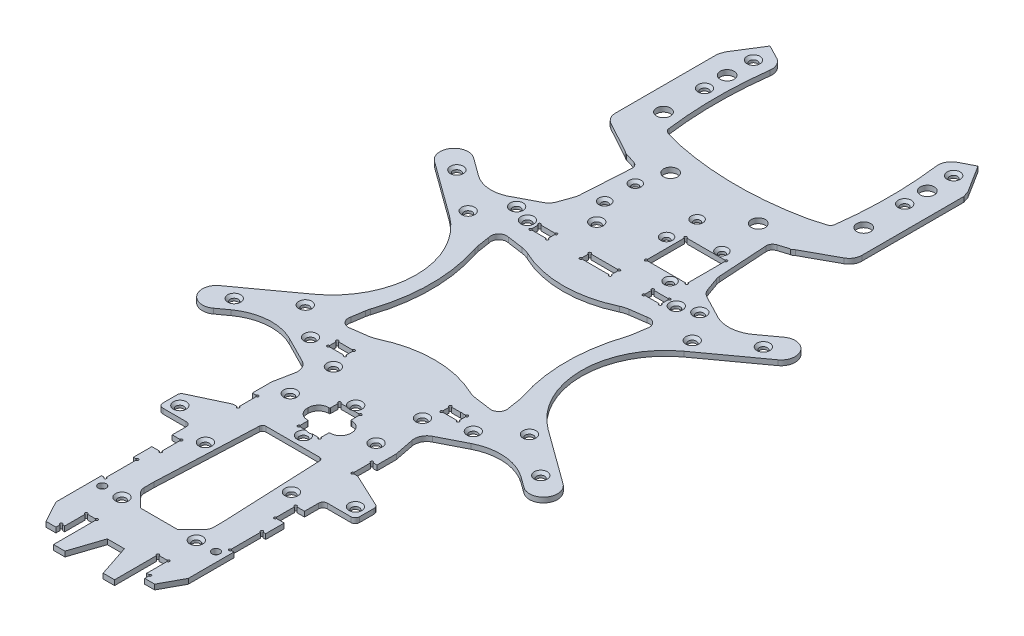
SolidWorks part; units mm, degrees
other "细节项目1"
other "细节项目5"
material "Thornel VCB-20 碳布"
ref_plane "前视基准面" through (0, 0, 0) normal (0, 0, 1) x (1, 0, 0)
ref_plane "上视基准面" through (0, 0, 0) normal (0, 1, 0) x (1, 0, 0)
ref_plane "右视基准面" through (0, 0, 0) normal (1, 0, 0) x (0, 0, -1)
sketch "草图1" plane through (0, 0, 0) normal (0, 1, 0) x (1, 0, 0)
  line L0 (-126.4995, 0) -> (116.8967, 0) construction
  line L1 (121.619, 121.619) -> (-121.619, -121.619) construction
  line L2 (0, 104.5414) -> (0, -99.6328) construction
  line L3 (-108.3893, 108.3893) -> (124.9236, -124.9236) construction
  line L4 (0, 0) -> (86.3378, -62.728) construction
  line L5 (15.4, 65.75) -> (23.6, 65.75)
  line L6 (15.4, 50.25) -> (15.4, 65.75)
  line L19 (15.4, 50.25) -> (23.6, 50.25)
  line L20 (30.4719, 81.4909) -> (48.4165, 91.3178)
  line L21 (0, 82.79) -> (0, 88.225) construction
  line L23 (-25.278, 96.1016) -> (-31.2014, 97.7723)
  line L25 (24.5, -95.1) -> (26.0011, -95.1) construction
  line L35 (67.5025, -42.245) -> (46.103, -26.6974)
  line L38 (-16.7464, -105.1066) -> (-17.9066, -103.9464) construction
  line L39 (-48.4165, 91.3178) -> (-48.4165, 134.3222)
  line L40 (-30.4719, 81.4909) -> (-48.4165, 91.3178)
  line L42 (26.0011, -95.1) -> (26.0011, -102.35)
  line L59 (-47.6512, 136.6895) -> (-40.8695, 147.4648)
  line L64 (15.4, 58) -> (27.0301, 58) construction
  line L65 (19.5, 65.75) -> (19.5, 50.25) construction
  line L66 (23.6, 65.75) -> (23.6, 50.25)
  line L69 (-39.335, 68.135) -> (3.7462, 68.135) construction
  line L72 (26.0011, -102.35) -> (22.5, -102.35)
  line L80 (-18.6137, -103.9464) -> (-19.7036, -105.0363) construction
  line L82 (4.1009, -74) -> (4.1009, -71.0475)
  line L83 (-3.6009, -74.5) -> (3.6009, -74.5)
  line L84 (3.6009, -58.5) -> (-3.5991, -58.5)
  line L85 (4.1009, -59) -> (4.1009, -61.9525)
  line L86 (-4.1009, -74) -> (-4.1009, -71.0461)
  line L87 (-4.1009, -61.9511) -> (-4.1009, -58.9981)
  line L88 (-4.5484, -70.6961) -> (-4.4509, -70.6961)
  line L89 (-8.5484, -66.6961) -> (-8.5484, -66.3011)
  line L90 (8.5484, -66.6975) -> (8.5484, -66.3025)
  line L91 (4.4509, -70.6975) -> (4.5484, -70.6975)
  line L92 (4.5484, -62.3025) -> (4.4509, -62.3025)
  line L93 (-4.5484, -62.3011) -> (-4.4509, -62.3011)
  line L97 (19, -62.5) -> (19, -100.5) construction
  line L98 (19, -100.5) -> (-19, -100.5) construction
  line L99 (-19, -62.5) -> (-19, -100.5) construction
  line L100 (22.5, -102.35) -> (22.5, -110.35)
  line L101 (16.1, -146) -> (16.1, -154.5)
  line L102 (16.1, -146) -> (12, -146)
  line L103 (12, -146) -> (12, -163)
  line L104 (17.45, -154.5) -> (16.1, -154.5)
  line L105 (17.45, -156.6) -> (17.45, -154.5)
  line L106 (-3.3584, -150.5) -> (-7.5, -163)
  line L107 (-7.5, -163) -> (-12, -163)
  line L108 (21.3534, -156.6) -> (17.45, -156.6)
  line L109 (-17.45, -156.6) -> (-17.45, -154.5)
  line L110 (-17.45, -154.5) -> (-16.1, -154.5)
  line L111 (-12, -146) -> (-12, -163)
  line L112 (-16.1, -146) -> (-12, -146)
  line L113 (-16.1, -146) -> (-16.1, -154.5)
  line L114 (7.5, -163) -> (12, -163)
  line L115 (-3.3584, -150.5) -> (3.3584, -150.5)
  line L116 (3.3584, -150.5) -> (7.5, -163)
  line L117 (-21.3534, -156.6) -> (-17.45, -156.6)
  line L118 (-13.5761, -121.8546) -> (-11.8487, -82.2911)
  line L119 (-12.5918, -128.1539) -> (-7.25, -133.5)
  line L120 (-7.25, -133.5) -> (7.25, -133.5)
  line L121 (-13.5793, -125.7684) -> (-13.5793, -122.0018)
  line L122 (22.5, -110.35) -> (26.0011, -110.35)
  line L123 (26.0011, -130.1) -> (26.0011, -148.0463)
  line L124 (26.0011, -148.0463) -> (21.3534, -156.6)
  line L125 (-26.0011, -148.0463) -> (-21.3534, -156.6)
  line L126 (-26.0011, -130.1) -> (-26.0011, -148.0463)
  line L127 (26.0011, -110.35) -> (26.0011, -117.6)
  line L128 (26.0011, -117.6) -> (24.5011, -117.6)
  line L129 (24.5011, -117.6) -> (24.5011, -130.1)
  line L130 (24.5011, -130.1) -> (26.0011, -130.1)
  line L132 (-24.5011, -130.1) -> (-26.0011, -130.1)
  line L133 (-24.5011, -117.6) -> (-24.5011, -130.1)
  line L134 (-26.0011, -117.6) -> (-24.5011, -117.6)
  line L135 (-26.0011, -110.35) -> (-26.0011, -117.6)
  line L136 (-22.5, -110.35) -> (-26.0011, -110.35)
  line L137 (-22.5, -102.35) -> (-22.5, -110.35)
  line L138 (-26.0011, -102.35) -> (-22.5, -102.35)
  line L139 (-26.0011, -95.1) -> (-26.0011, -102.35)
  line L140 (-24.5, -95.1) -> (-26.0011, -95.1) construction
  line L142 (-67.5025, 42.245) -> (-46.103, 26.6974)
  line L143 (-67.5025, -42.245) -> (-46.103, -26.6974)
  line L149 (48.4165, 91.3178) -> (48.4165, 134.3222)
  line L150 (0, -114.8485) -> (0, -146.3095) construction
  line L151 (-10.5, -81) -> (10.5, -81)
  line L152 (12.5918, -128.1539) -> (7.25, -133.5)
  line L153 (13.5793, -125.7684) -> (13.5793, -122.0018)
  line L154 (13.5761, -121.8546) -> (11.8487, -82.2911)
  line L155 (-19, -62.5) -> (19, -62.5) construction
  line L180 (67.5025, 42.245) -> (46.103, 26.6974)
  line L181 (44.0442, 32) -> (60.2246, 43.7557) construction
  line L183 (25.278, 96.1016) -> (31.2014, 97.7723)
  line L195 (61.0368, 51.1442) -> (53.9618, 46.0039)
  line L196 (30.4719, 81.4909) -> (34.3794, 54.2815)
  line L197 (-30.4719, 81.4909) -> (-34.3794, 54.2815)
  line L198 (-61.0368, 51.1442) -> (-53.9618, 46.0039)
  line L199 (57.02, -48.2258) -> (61.0368, -51.1442)
  line L200 (24.5, -64.7956) -> (24.5, -95.1) construction
  line L201 (-24.5, -64.7956) -> (-24.5, -95.1) construction
  line L202 (-57.02, -48.2258) -> (-61.0368, -51.1442)
  line L203 (26.0011, -95.1) -> (38.6804, -95.1)
  line L204 (38.6804, -95.1) -> (38.6804, -86.6)
  line L205 (38.6804, -86.6) -> (24.5, -79.9478)
  line L207 (-38.6804, -86.6) -> (-24.5, -79.9478)
  line L208 (-38.6804, -95.1) -> (-38.6804, -86.6)
  line L209 (-26.0011, -95.1) -> (-38.6804, -95.1)
  line L210 (-24.5, -64.7956) -> (-24.5, -79.9478) construction
  line L211 (-19.7036, -114.2434) -> (-18.5434, -115.4036) construction
  line L212 (-17.8363, -115.4036) -> (-16.7464, -114.3137) construction
  line L213 (-19.85, -105.3898) -> (-19.85, -113.8898) construction
  line L214 (-16.6, -105.4602) -> (-16.6, -113.9602) construction
  line L221 (-16.6, -105.4602) -> (-16.6, -108.5148) construction
  line L222 (-16.6, -108.5148) -> (-17.1, -109.0148) construction
  line L223 (-17.1, -109.0148) -> (-17.1, -110.2648) construction
  line L224 (-17.1, -110.2648) -> (-16.6, -110.7648) construction
  line L225 (-16.6, -110.7648) -> (-16.6, -113.9602) construction
  line L226 (-19.85, -109.6398) -> (-13.2317, -109.6398) construction
  line L227 (17.1, -110.2648) -> (16.6, -110.7648) construction
  line L228 (17.1, -109.0148) -> (17.1, -110.2648) construction
  line L229 (16.6, -108.5148) -> (17.1, -109.0148) construction
  line L230 (16.6, -105.4602) -> (16.6, -108.5148) construction
  line L231 (16.7464, -105.1066) -> (17.9066, -103.9464) construction
  line L232 (18.6137, -103.9464) -> (19.7036, -105.0363) construction
  line L233 (19.85, -105.3898) -> (19.85, -113.8898) construction
  line L234 (19.7036, -114.2434) -> (18.5434, -115.4036) construction
  line L235 (17.8363, -115.4036) -> (16.7464, -114.3137) construction
  line L236 (16.6, -110.7648) -> (16.6, -113.9602) construction
  line L237 (-24.5, -72.3717) -> (-22.5, -72.3717)
  line L238 (-22.5, -72.3717) -> (-22.5, -79.9478)
  line L239 (-22.5, -79.9478) -> (-24.5, -79.9478)
  line L240 (-24.5, -64.7956) -> (-24.5, -72.3717)
  line L241 (22.5, -79.9478) -> (24.5, -79.9478)
  line L242 (24.5, -64.7956) -> (24.5, -72.3717)
  line L243 (24.5, -72.3717) -> (22.5, -72.3717)
  line L244 (22.5, -72.3717) -> (22.5, -79.9478)
  line L245 (-40.8695, 147.4648) -> (-35.5107, 144.7028)
  line L246 (-47.6512, 136.6895) -> (-48.4165, 134.3222)
  line L247 (40.8695, 147.4648) -> (35.5107, 144.7028)
  line L248 (47.6512, 136.6895) -> (40.8695, 147.4648)
  line L249 (47.6512, 136.6895) -> (48.4165, 134.3222)
  circle A0 centre (10, 10) radius 1.075
  circle A1 centre (12.75, 12.75) radius 1.075
  circle A2 centre (15.25, 15.25) radius 1.55
  circle A3 centre (-15.25, 15.25) radius 1.55
  circle A4 centre (-12.75, 12.75) radius 1.075
  circle A5 centre (-10, 10) radius 1.075
  circle A6 centre (-10, -10) radius 1.075
  circle A7 centre (-12.75, -12.75) radius 1.075
  circle A8 centre (-15.25, -15.25) radius 1.55
  circle A9 centre (15.25, -15.25) radius 1.55
  circle A10 centre (12.75, -12.75) radius 1.075
  circle A11 centre (10, -10) radius 1.075
  circle A14 centre (28, -28) radius 3.15
  circle A15 centre (-28, -28) radius 3.15
  circle A16 centre (19.5, 68.2) radius 1.3
  circle A31 centre (19.5, 47.8) radius 1.3
  circle A34 centre (17.238, 84.7633) radius 2.75
  circle A35 centre (-17.238, 84.7633) radius 2.75
  circle A36 centre (-39.335, 104.0823) radius 2.75
  circle A37 centre (-39.335, 129.0823) radius 2.75
  circle A38 centre (-28, 28) radius 3.15
  circle A39 centre (28, 28) radius 3.15
  circle A43 centre (44.0442, -32) radius 1.55
  circle A44 centre (60.2246, -43.7557) radius 1.55
  circle A47 centre (-60.2246, -43.7557) radius 1.55
  circle A65 centre (-20.5, 74.15) radius 1.3
  circle A68 centre (-20.5, 62.12) radius 1.3
  circle A71 centre (-44.0442, -32) radius 1.55
  circle A72 centre (60.2246, 43.7557) radius 1.55
  circle A73 centre (44.0442, 32) radius 1.55
  circle A74 centre (-44.0442, 32) radius 1.55
  circle A75 centre (-60.2246, 43.7557) radius 1.55
  arc A77 (61.0368, -51.1442) -> (67.5025, -42.245) centre (64.2696, -46.6946) ccw
  arc A82 (-16.6, -105.4602) -> (-16.7464, -105.1066) centre (-17.1, -105.4602) ccw construction
  arc A83 (-17.9066, -103.9464) -> (-18.6137, -103.9464) centre (-18.2602, -104.3) ccw construction
  arc A84 (-19.85, -105.3898) -> (-19.7036, -105.0363) centre (-19.35, -105.3898) cw construction
  arc A85 (-4.1009, -74) -> (-3.6009, -74.5) centre (-4.1009, -74.5) ccw
  arc A86 (4.1009, -74) -> (3.6009, -74.5) centre (4.1009, -74.5) cw
  arc A87 (4.1009, -59) -> (3.6009, -58.5) centre (4.1009, -58.5) ccw
  arc A88 (-4.1009, -58.9981) -> (-3.5991, -58.5) centre (-4.0991, -58.4981) cw
  arc A89 (8.5484, -66.3025) -> (4.5484, -62.3025) centre (4.5484, -66.3025) ccw
  arc A90 (-4.5484, -62.3011) -> (-8.5484, -66.3011) centre (-4.5484, -66.3011) ccw
  arc A91 (-4.5484, -70.6961) -> (-8.5484, -66.6961) centre (-4.5484, -66.6961) cw
  arc A92 (8.5484, -66.6975) -> (4.5484, -70.6975) centre (4.5484, -66.6975) cw
  arc A93 (4.1009, -61.9525) -> (4.4509, -62.3025) centre (4.4509, -61.9525) ccw
  arc A94 (4.1009, -71.0475) -> (4.4509, -70.6975) centre (4.4509, -71.0475) cw
  arc A95 (-4.1009, -61.9511) -> (-4.4509, -62.3011) centre (-4.4509, -61.9511) cw
  arc A96 (-4.1009, -71.0461) -> (-4.4509, -70.6961) centre (-4.4509, -71.0461) ccw
  circle A103 centre (-22.35, -133.5) radius 1.55
  circle A104 centre (22.35, -133.5) radius 1.55
  circle A105 centre (-16.9, -98.4) radius 1.55
  circle A106 centre (16.9, -98.4) radius 1.55
  arc A107 (-10.5, -81) -> (-11.8487, -82.2911) centre (-10.5, -82.35) ccw
  arc A108 (-13.5793, -122.0018) -> (-13.5761, -121.8546) centre (-10.2043, -122.0018) cw
  arc A109 (-12.5918, -128.1539) -> (-13.5793, -125.7684) centre (-10.2043, -125.7684) cw
  circle A110 centre (-14.6, -133.5) radius 1.55
  circle A111 centre (14.6, -133.5) radius 1.55
  arc A112 (12.5918, -128.1539) -> (13.5793, -125.7684) centre (10.2043, -125.7684) ccw
  arc A113 (13.5793, -122.0018) -> (13.5761, -121.8546) centre (10.2043, -122.0018) ccw
  arc A114 (10.5, -81) -> (11.8487, -82.2911) centre (10.5, -82.35) cw
  circle A143 centre (-16.866, -65.108) radius 1.55
  circle A144 centre (16.866, -65.108) radius 1.55
  circle A145 centre (0, -56.25) radius 1.55
  circle A146 centre (0, -76.75) radius 1.55
  arc A147 (61.0368, 51.1442) -> (67.5025, 42.245) centre (64.2696, 46.6946) cw
  arc A148 (46.103, 26.6974) -> (46.103, -26.6974) centre (65.4998, 0) ccw
  circle A149 centre (44.0442, -32) radius 6 construction
  arc A151 (-61.0368, 51.1442) -> (-67.5025, 42.245) centre (-64.2696, 46.6946) ccw
  arc A153 (-46.103, 26.6974) -> (-46.103, -26.6974) centre (-65.4998, 0) cw
  arc A154 (-61.0368, -51.1442) -> (-67.5025, -42.245) centre (-64.2696, -46.6946) cw
  circle A158 centre (39.335, 129.0823) radius 2.75
  circle A159 centre (39.335, 104.0823) radius 2.75
  arc A160 (-25.278, 96.1016) -> (25.278, 96.1016) centre (0, 215.2587) ccw
  circle A161 centre (-36, 43) radius 1.55
  circle A164 centre (36, 43) radius 1.55
  circle A165 centre (-32, -42) radius 1.55
  circle A166 centre (32, -42) radius 1.55
  circle A171 centre (-39.335, 139.4323) radius 1.55
  arc A178 (32.6754, 139.3072) -> (32.6419, 99.4401) centre (-122.1129, 119.5036) cw
  arc A180 (-32.6754, 139.3072) -> (-32.6419, 99.4401) centre (122.1129, 119.5036) ccw
  arc A182 (53.9618, 46.0039) -> (34.3794, 54.2815) centre (46.6659, 56.0459) cw
  arc A183 (-53.9618, 46.0039) -> (-34.3794, 54.2815) centre (-46.6659, 56.0459) ccw
  circle A185 centre (39.335, 139.4323) radius 1.55
  arc A186 (57.02, -48.2258) -> (24.5, -64.7956) centre (44.9813, -64.7956) ccw
  arc A187 (-57.02, -48.2258) -> (-24.5, -64.7956) centre (-44.9813, -64.7956) cw
  circle A188 centre (34.5, -90.85) radius 1.55
  circle A189 centre (-34.5, -90.85) radius 1.55
  circle A190 centre (39.335, 120.1823) radius 1.55
  circle A191 centre (-39.335, 120.1823) radius 1.55
  arc A192 (-19.85, -113.8898) -> (-19.7036, -114.2434) centre (-19.35, -113.8898) ccw construction
  arc A193 (-18.5434, -115.4036) -> (-17.8363, -115.4036) centre (-18.1898, -115.05) ccw construction
  arc A194 (-16.6, -113.9602) -> (-16.7464, -114.3137) centre (-17.1, -113.9602) cw construction
  arc A195 (16.6, -105.4602) -> (16.7464, -105.1066) centre (17.1, -105.4602) cw construction
  arc A196 (17.9066, -103.9464) -> (18.6137, -103.9464) centre (18.2602, -104.3) cw construction
  arc A197 (19.85, -105.3898) -> (19.7036, -105.0363) centre (19.35, -105.3898) ccw construction
  arc A198 (19.85, -113.8898) -> (19.7036, -114.2434) centre (19.35, -113.8898) cw construction
  arc A199 (18.5434, -115.4036) -> (17.8363, -115.4036) centre (18.1898, -115.05) cw construction
  arc A200 (16.6, -113.9602) -> (16.7464, -114.3137) centre (17.1, -113.9602) ccw construction
  circle A201 centre (3.8, 62.12) radius 1.3
  circle A202 centre (3.8, 74.15) radius 1.3
  arc A203 (-35.5107, 144.7028) -> (-32.6754, 139.3072) centre (-37.9442, 139.9813) cw
  arc A204 (35.5107, 144.7028) -> (32.6754, 139.3072) centre (37.9442, 139.9813) ccw
  arc A205 (32.6419, 99.4401) -> (31.2014, 97.7723) centre (30.6585, 99.6972) cw
  arc A206 (-31.2014, 97.7723) -> (-32.6419, 99.4401) centre (-30.6585, 99.6972) cw
  point P55 (32.4663, 98.1291)
  point P77 (-32.4663, 98.1291)
  point P104 (-32.5, 0)
  point P105 (32.5, 0)
  point P214 (38.6804, -90.85)
  point P354 (0, -133.5)
  point P361 (7.3036, -118.1341)
  point P364 (0, -81)
  dimension "D2" = 2.15
  dimension "D5" = 3.1
  dimension "D7" = 3.1
  dimension "D8" = 36
  dimension "D10" = 39.335
  dimension "D11" = 3.1
  dimension "D20" = 2.6
  dimension "D22" = 3.1
  dimension "D32" = 7.25
  dimension "D12" = 24.3
  dimension "D15" = 3.25
  dimension "D13" = 19.85
  dimension "D9" = 3.1
  dimension "D25" = 5.5
  dimension "D26" = 5
  dimension "D31" = 12
  dimension "D41" = 96.833
  dimension "D49" = 32
  dimension "D54" = 35.35
  dimension "D59" = 8.5
  dimension "D61" = 6.3
  dimension "D70" = 2.6
  dimension "D69" = 156.05
  dimension "D71" = 2
  dimension "D84" = 24.735
  dimension "D3" = 10
  dimension "D4" = 2.75
  dimension "D6" = 2.5
  dimension "D14" = 58
  dimension "D16" = 2.608
  dimension "D17" = 15.5
  dimension "D18" = 2.45
  dimension "D19" = 8.2
  dimension "D21" = 12.03
  dimension "D23" = 2.25
  dimension "D24" = 2.25
  dimension "D27" = 20
  dimension "D28" = 25
  dimension "D29" = 19.5
  dimension "D30" = 32
  dimension "D33" = 1.5
  dimension "D34" = 2.1
  dimension "D35" = 8.5
  dimension "D36" = 4.5
  dimension "D37" = 4
  dimension "D38" = 4.1
  dimension "D39" = 8
  dimension "D40" = 65
  dimension "D42" = 10.5
  dimension "D43" = 43
  dimension "D44" = 52.5
  dimension "D45" = 58.5
  dimension "D46" = 7.2
  dimension "D47" = 16
  dimension "D48" = 62.5
  dimension "D50" = 38
  dimension "D51" = 139.4323
  dimension "D52" = 36
  dimension "D53" = 42
  dimension "D55" = 90.85
  dimension "D56" = 5.5
  dimension "D57" = 38
  dimension "D58" = 34.5
  dimension "D60" = 56
  dimension "D62" = 7.25
  dimension "D63" = 19.25
  dimension "D64" = 8.5
  dimension "D65" = 1.25
  dimension "D66" = 0.5
  dimension "D67" = 2
  dimension "D68" = 20.5
  dimension "D72" = 29.2
  dimension "D73" = 7.75
  dimension "D74" = 1.35
  dimension "D75" = 24
  dimension "D76" = 6.4
  dimension "D77" = 12.5
  dimension "D78" = 6.5
  dimension "D79" = 92.5
  dimension "D80" = 12.5
  dimension "D81" = 133.5
  dimension "D82" = 4.5
  dimension "D83" = 272.9323
extrude "凸台-拉伸1" add sketch "草图1" along normal blind 2
sketch "草图6" plane through (0, 2, 0) normal (0, 1, 0) x (1, 0, 0)
  line L40 (-58.8867, 0) -> (57.6096, 0) construction
  line L41 (0, 29.8455) -> (0, -115.5328) construction
  line L42 (22.5859, -13.8118) -> (4.3699, 0)
  line L43 (22.5859, 13.8118) -> (4.3699, 0)
  line L44 (-22.5859, 13.8118) -> (-4.3699, 0)
  line L45 (-22.5859, -13.8118) -> (-4.3699, 0)
  line L46 (-11.5388, -19.5881) -> (0, -4.3699)
  line L47 (11.5388, -19.5881) -> (0, -4.3699)
  line L48 (11.5388, 19.5881) -> (0, 4.3699)
  line L49 (-11.5388, 19.5881) -> (0, 4.3699)
  line L50 (0, 0) -> (43.5528, -43.5528) construction
  arc A48 (22.5859, 13.8118) -> (28.8648, 17.1963) centre (41.8919, -14.4887) cw
  arc A49 (28.8648, 17.1963) -> (28.8648, -17.1963) centre (91.8849, 0) ccw
  arc A50 (22.5859, -13.8118) -> (28.8648, -17.1963) centre (41.8919, 14.4887) ccw
  arc A51 (13.7761, -22.9243) -> (-13.7761, -22.9243) centre (0, -91.9966) ccw
  arc A52 (-22.5859, -13.8118) -> (-28.8648, -17.1963) centre (-41.8919, 14.4887) cw
  arc A53 (-28.8648, 17.1963) -> (-28.8648, -17.1963) centre (-91.8849, 0) cw
  arc A54 (-22.5859, 13.8118) -> (-28.8648, 17.1963) centre (-41.8919, -14.4887) ccw
  arc A55 (11.5388, -19.5881) -> (13.7761, -22.9243) centre (-16.057, -40.512) cw
  arc A56 (-11.5388, -19.5881) -> (-13.7761, -22.9243) centre (16.057, -40.512) ccw
  arc A57 (-11.5388, 19.5881) -> (-13.7761, 22.9243) centre (16.057, 40.512) cw
  arc A58 (13.7761, 22.9243) -> (-13.7761, 22.9243) centre (0, 91.9966) cw
  arc A59 (11.5388, 19.5881) -> (13.7761, 22.9243) centre (-16.057, 40.512) ccw
  point P79 (0, 0)
extrude "减重" cut sketch "草图6" against normal up to next
sketch "减重-2-草图" plane through (0, 0, 0) normal (0, 1, 0) x (1, 0, 0)
  line L0 (-20.9845, 30.1828) -> (-28, 31.15)
  line L1 (-31.15, 28) -> (-30.2498, 22.1218)
  line L2 (0, 0) -> (-85.1983, 0) construction
  line L3 (0, 0) -> (0, 222.2014) construction
  line L4 (31.15, 28) -> (30.2498, 22.1218)
  line L5 (20.9845, 30.1828) -> (28, 31.15)
  line L6 (20.9845, -30.1828) -> (28, -31.15)
  line L7 (31.15, -28) -> (30.2498, -22.1218)
  line L8 (-31.15, -28) -> (-30.2498, -22.1218)
  line L9 (-20.9845, -30.1828) -> (-28, -31.15)
  circle A0 centre (-28, 28) radius 3.15 construction
  arc A1 (-31.15, 28) -> (-28, 31.15) centre (-28, 28) cw
  arc A2 (31.15, 28) -> (28, 31.15) centre (28, 28) ccw
  arc A3 (31.15, -28) -> (28, -31.15) centre (28, -28) cw
  arc A4 (-31.15, -28) -> (-28, -31.15) centre (-28, -28) ccw
  arc A5 (-29.86, 20.4977) -> (-29.86, -20.4977) centre (-91.8849, 0) cw
  arc A6 (-18.059, -29.3089) -> (18.059, -29.3089) centre (0, -67.3193) cw
  arc A7 (29.86, -20.4977) -> (29.86, 20.4977) centre (91.8849, 0) cw
  arc A8 (-18.059, 29.3089) -> (18.059, 29.3089) centre (0, 67.3193) ccw
  arc A9 (-28.8648, -17.1963) -> (-28.8648, 17.1963) centre (-91.8849, 0) ccw construction
  arc A10 (28.8648, 17.1963) -> (28.8648, -17.1963) centre (91.8849, 0) ccw construction
  arc A13 (30.2498, -22.1218) -> (29.86, -20.4977) centre (20.3651, -23.6355) ccw
  arc A14 (20.9845, -30.1828) -> (18.059, -29.3089) centre (22.3504, -20.2765) cw
  arc A15 (-20.9845, -30.1828) -> (-18.059, -29.3089) centre (-22.3504, -20.2765) ccw
  arc A16 (-30.2498, -22.1218) -> (-29.86, -20.4977) centre (-20.3651, -23.6355) cw
  arc A17 (30.2498, 22.1218) -> (29.86, 20.4977) centre (20.3651, 23.6355) cw
  arc A18 (-30.2498, 22.1218) -> (-29.86, 20.4977) centre (-20.3651, 23.6355) ccw
  arc A19 (20.9845, 30.1828) -> (18.059, 29.3089) centre (22.3504, 20.2765) ccw
  arc A20 (-20.9845, 30.1828) -> (-18.059, 29.3089) centre (-22.3504, 20.2765) cw
  point P39 (30.1184, -21.2637)
  point P42 (19.3706, -29.9602)
  point P45 (-19.3706, -29.9602)
  point P48 (-30.1184, -21.2637)
  point P51 (30.1184, 21.2637)
  point P54 (-30.1184, 21.2637)
  point P57 (19.3706, 29.9602)
  point P60 (-19.3706, 29.9602)
  dimension "D1" = 10
extrude "切除-拉伸2" cut sketch "减重-2-草图" along normal through all both and the other way through all
fillet "圆角1" radius 5 6 edges at (-25.278, 1, -96.1016) (25.278, 1, -96.1016) (48.4165, 1, -91.3178) (-48.4165, 1, -91.3178) (-30.4719, 1, -81.4909) (30.4719, 1, -81.4909)
sketch "草图7" plane through (0, 2, 0) normal (0, 1, 0) x (1, 0, 0)
  line L0 (-81.2345, 0) -> (102.1666, 0) construction
  line L1 (0, 63.5408) -> (0, -83.9036) construction
  line L2 (34, -3.25) -> (30.5, -3.25) construction
  line L3 (-34, 3.25) -> (-30.5, 3.25) construction
  line L4 (-34, 3.25) -> (-34, -3.25) construction
  line L5 (-34, -3.25) -> (-30.5, -3.25) construction
  line L6 (-30.5, 3.25) -> (-30.5, -3.25) construction
  line L7 (30.5, 3.25) -> (30.5, -3.25) construction
  line L8 (34, 3.25) -> (30.5, 3.25) construction
  line L9 (34, 3.25) -> (34, -3.25) construction
  line L10 (19, -38) -> (25.5, -38)
  line L11 (-25.5, 41.5) -> (-19, 41.5)
  line L12 (-25.5, 41.5) -> (-25.5, 38)
  line L13 (-25.5, 38) -> (-19, 38)
  line L14 (-19, 41.5) -> (-19, 38)
  line L15 (19, -38) -> (19, -41.5)
  line L16 (19, -41.5) -> (25.5, -41.5)
  line L17 (25.5, -38) -> (25.5, -41.5)
  line L18 (-19, -38) -> (-19, -41.5)
  line L19 (-19, -41.5) -> (-25.5, -41.5)
  line L20 (-25.5, -38) -> (-25.5, -41.5)
  line L21 (-19, -38) -> (-25.5, -38)
  line L22 (25.5, 38) -> (19, 38)
  line L23 (19, 41.5) -> (19, 38)
  line L24 (25.5, 41.5) -> (19, 41.5)
  line L25 (25.5, 41.5) -> (25.5, 38)
  line L26 (-5.75, -38) -> (5.75, -38) construction
  line L27 (5.75, -38) -> (5.75, -41.5) construction
  line L28 (5.75, -41.5) -> (-5.75, -41.5) construction
  line L29 (-5.75, -41.5) -> (-5.75, -38) construction
  line L30 (5.75, 41.5) -> (-5.75, 41.5)
  line L31 (5.75, 38) -> (5.75, 41.5)
  line L32 (-5.75, 38) -> (5.75, 38)
  line L33 (-5.75, 41.5) -> (-5.75, 38)
  point P26 (19, -39.75)
  dimension "D1" = 3.5
  dimension "D2" = 6.5
  dimension "D3" = 30.5
  dimension "D4" = 38
  dimension "D5" = 19
  dimension "D6" = 38
  dimension "D7" = 5.75
extrude "保护壳固定点" cut sketch "草图7" against normal up to next
sketch "草图8" plane through (0, 0, 0) normal (0, 1, 0) x (1, 0, 0)
  line L1 (15.4, 50.25) -> (23.6, 50.25) construction
  line L5 (0, 0) -> (0, 133.3353) construction
  line L6 (0, 0) -> (133.1914, 0) construction
  line L7 (7.65, 65.75) -> (15.4, 65.75)
  line L8 (15.4, 65.75) -> (15.4, 50.25) construction
  line L9 (15.4, 65.75) -> (15.4, 50.25)
  line L10 (15.4, 50.25) -> (7.65, 50.25)
  line L11 (7.65, 50.25) -> (7.65, 65.75)
  line L12 (14.15, 65.75) -> (14.15, 50.25) construction
  circle A0 centre (23.5, -39.4628) radius 1.55
  circle A1 centre (0, -56.25) radius 1.55 construction
  circle A2 centre (-29.25, 40.5) radius 1.55
  circle A4 centre (-17.5, -47.5) radius 1.55
  circle A6 centre (29.25, 40.5) radius 1.55
  circle A7 centre (17.5, -47.5) radius 1.55
  circle A8 centre (29.25, 40.5) radius 1.55
  dimension "D3" = 3.1
  dimension "D9" = 40.5
  dimension "D12" = 3.1
  dimension "D1" = 16.7872
  dimension "D2" = 23.5
  dimension "D4" = 1.25
  dimension "D6" = 6.5
  dimension "D7" = 15.5
  dimension "D8" = 29.25
  dimension "D10" = 47.5
  dimension "D11" = 17.5
extrude "计算机板接口和分电PCB接口" cut sketch "草图8" along normal through all contours L11 L10 L9 L7 | A2 | A4 | A7 | A6 | A0 | A0 region at (11.525, 0, -58) region at (23.5, 0, 39.4628) region at (-29.25, 0, -40.5) region at (-17.5, 0, 47.5) region at (29.25, 0, -40.5) region at (17.5, 0, 47.5)
fillet "圆角2" radius 1.75 8 edges at (-26.0011, 1, 95.1) (-38.6804, 1, 95.1) (-38.6804, 1, 86.6) (38.6804, 1, 86.6) (38.6804, 1, 95.1) (26.0011, 1, 95.1) (24.5, 1, 79.9478) (-24.5, 1, 79.9478)
sketch "草图12" plane through (0, 0, 0) normal (0, 1, 0) x (1, 0, 0)
  line L0 (26.7, 40.5) -> (-26.7, 40.5) construction
  circle A10 centre (-15, 53.5) radius 1.55
  dimension "D1" = 3.1
  dimension "D2" = 53.5
  dimension "D3" = 15
extrude "计算机板安装孔-旧的太难用了" cut sketch "草图12" along normal through all
sketch "边缘二次裁切-减重-草图" plane through (0, 0, 0) normal (0, 1, 0) x (1, 0, 0)
  line L0 (-26.3691, 78.6288) -> (-27.5605, 59.15)
  line L1 (-27.8403, 57.7795) -> (-29.754, 52.4001)
  line L2 (-32.155, 49.6414) -> (-41.6968, 44.6713)
  line L3 (-28.11, 81.1649) -> (-32.2962, 82.4899)
  line L4 (-32.2962, 82.4899) -> (-41.6968, 44.6713)
  line L5 (0, 0) -> (0, 176.889) construction
  line L6 (-26.25, 80.5762) -> (-26.25, 105.0808) construction
  line L7 (28.11, 81.1649) -> (32.2962, 82.4899)
  line L8 (26.3691, 78.6288) -> (27.5605, 59.15)
  line L9 (27.8403, 57.7795) -> (29.754, 52.4001)
  line L10 (32.155, 49.6414) -> (41.6968, 44.6713)
  line L11 (32.2962, 82.4899) -> (41.6968, 44.6713)
  line L12 (-35.683, -46.5466) -> (-25.6169, -51.6755)
  line L13 (-22.9814, -57.0983) -> (-24.5, -64.7956)
  line L14 (-22.25, -53.391) -> (-22.25, -41.5) construction
  line L15 (-35.683, -46.5466) -> (-35.683, -64.7956)
  line L16 (-35.683, -64.7956) -> (-24.5, -64.7956)
  line L21 (-45.8181, 89.8949) -> (-33.5123, 83.1559) construction
  line L22 (35.683, -46.5466) -> (25.6169, -51.6755)
  line L23 (35.683, -46.5466) -> (35.683, -64.7956)
  line L24 (35.683, -64.7956) -> (24.5, -64.7956)
  line L25 (22.9814, -57.0983) -> (24.5, -64.7956)
  line L28 (0, 0) -> (-89.0445, 0) construction
  line L29 (-13.8246, 34.5028) -> (0, 30.5288) construction
  line L32 (-13.8246, 34.5028) -> (-11.6065, 42.2193) construction
  line L33 (-11.6065, 42.2193) -> (0, 44.9377) construction
  line L34 (13.8246, 34.5028) -> (0, 30.5288) construction
  line L35 (13.8246, 34.5028) -> (11.6065, 42.2193) construction
  line L36 (11.6065, 42.2193) -> (0, 44.9377) construction
  arc A3 (-26.3691, 78.6288) -> (-28.11, 81.1649) centre (-28.8644, 78.7815) ccw
  arc A4 (-29.754, 52.4001) -> (-32.155, 49.6414) centre (-34.4648, 54.0759) cw
  arc A5 (-27.5605, 59.15) -> (-27.8403, 57.7795) centre (-32.5512, 59.4553) cw
  arc A6 (26.3691, 78.6288) -> (28.11, 81.1649) centre (28.8644, 78.7815) cw
  arc A7 (27.5605, 59.15) -> (27.8403, 57.7795) centre (32.5512, 59.4553) ccw
  arc A8 (29.754, 52.4001) -> (32.155, 49.6414) centre (34.4648, 54.0759) ccw
  circle A10 centre (-17.5, -47.5) radius 1.55 construction
  arc A11 (-53.9618, 46.0039) -> (-34.3794, 54.2815) centre (-46.6659, 56.0459) ccw construction
  arc A12 (-24.5, -64.7956) -> (-57.02, -48.2258) centre (-44.9813, -64.7956) ccw construction
  arc A13 (-25.6169, -51.6755) -> (-22.9814, -57.0983) centre (-27.8869, -56.1305) cw
  arc A14 (25.6169, -51.6755) -> (22.9814, -57.0983) centre (27.8869, -56.1305) ccw
  circle A15 centre (-20.5, 74.15) radius 1.3 construction
  point P24 (-27.6036, 58.445)
  point P56 (-35.683, -46.5466)
  dimension "D4" = 2.5
  dimension "D5" = 5
  dimension "D1" = 5
  dimension "D7" = 15
  dimension "D2" = 3.5
  dimension "D3" = 5.75
  dimension "D6" = 4.75
chamfer "沉头螺丝位" distance 1 angle 45 37 edges at (14.6, 2, 135.05) (-14.6, 2, 131.95) (0, 2, 57.8) (0, 2, 78.3) (19.5, 2, -49.1) (19.5, 2, -69.5) (-20.5, 2, -63.42) (-20.5, 2, -72.85) (60.2246, 2, -45.3057) (44.0442, 2, -33.55) (36, 2, -44.55) (-60.2246, 2, -42.2057) (-36, 2, -41.45) (-44.0442, 2, -30.45) (-32, 2, 43.55) (-44.0442, 2, 30.45) (-60.2246, 2, 42.2057) (60.2246, 2, 45.3057) (44.0442, 2, 33.55) (32, 2, 40.45) (16.866, 2, 63.558) (-16.866, 2, 66.658) (-16.9, 2, 99.95) (16.9, 2, 96.85) (34.5, 2, 92.4) (-34.5, 2, 89.3) (39.335, 2, -137.8823) (-39.335, 2, -137.8823) (29.25, 2, -38.95) (-29.25, 2, -38.95) (-17.5, 2, 49.05) (17.5, 2, 49.05) (39.335, 2, -118.6323) (-39.335, 2, -121.7323) (3.8, 2, -75.45) (3.8, 2, -60.82) (-15, 2, -51.95)
extrude "边缘二次裁切-减重" cut sketch "边缘二次裁切-减重-草图" along normal through all
sketch "这个是因为刀切不了直角" plane through (0, 2, 0) normal (0, 1, 0) x (1, 0, 0)
  line L0 (-5.75, 41.5) -> (-5.75, 38) construction
  line L1 (-17.45, -156.6) -> (-17.45, -154.5) construction
  line L2 (0, 0) -> (0, -194.9857) construction
  circle A0 centre (7.65, 65.75) radius 0.5
  circle A1 centre (7.65, 50.25) radius 0.5
  circle A2 centre (-25.5, 41.5) radius 0.5
  circle A3 centre (-19, 41.5) radius 0.5
  circle A4 centre (-25.5, 38) radius 0.5
  circle A5 centre (-19, 38) radius 0.5
  circle A31 centre (-22.5, -72.3717) radius 0.5
  circle A33 centre (-22.5, -79.9478) radius 0.5
  circle A35 centre (-22.5, -102.35) radius 0.5
  circle A37 centre (-22.5, -110.35) radius 0.5
  circle A39 centre (-24.5011, -117.6) radius 0.5
  circle A40 centre (-16.1, -146) radius 0.5
  circle A41 centre (-24.5011, -130.1) radius 0.5
  circle A42 centre (-12, -146) radius 0.5
  circle A43 centre (-17.45, -154.5) radius 0.5
  circle A47 centre (17.45, -154.5) radius 0.5
  circle A48 centre (12, -146) radius 0.5
  circle A49 centre (24.5011, -130.1) radius 0.5
  circle A50 centre (16.1, -146) radius 0.5
  circle A51 centre (24.5011, -117.6) radius 0.5
  circle A52 centre (22.5, -110.35) radius 0.5
  circle A53 centre (22.5, -102.35) radius 0.5
  circle A54 centre (22.5, -79.9478) radius 0.5
  circle A55 centre (22.5, -72.3717) radius 0.5
  circle A62 centre (19, 38) radius 0.5
  circle A63 centre (25.5, 38) radius 0.5
  circle A64 centre (19, 41.5) radius 0.5
  circle A65 centre (25.5, 41.5) radius 0.5
  circle A72 centre (23.6, 65.75) radius 0.5
  circle A73 centre (23.6, 50.25) radius 0.5
  circle A78 centre (-25.5, -38) radius 0.5
  circle A79 centre (-25.5, -41.5) radius 0.5
  circle A80 centre (-19, -38) radius 0.5
  circle A81 centre (-19, -41.5) radius 0.5
  circle A82 centre (19, -38) radius 0.5
  circle A83 centre (19, -41.5) radius 0.5
  circle A84 centre (25.5, -38) radius 0.5
  circle A85 centre (25.5, -41.5) radius 0.5
  circle A86 centre (-5.75, 41.5) radius 0.5
  circle A87 centre (-5.75, 38) radius 0.5
  circle A88 centre (5.75, 41.5) radius 0.5
  circle A89 centre (5.75, 38) radius 0.5
  dimension "D1" = 1
extrude "直角约束" cut sketch "这个是因为刀切不了直角" against normal through all
